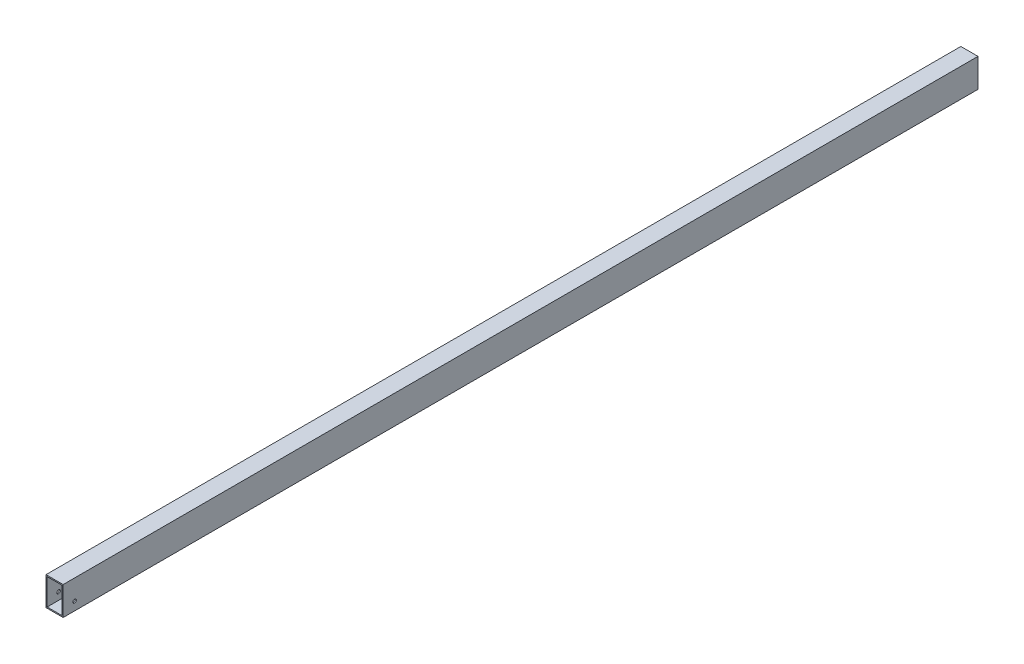
SolidWorks part; units mm, degrees
material "1060 合金"
ref_plane "前视基准面" through (0, 0, 0) normal (0, 0, 1) x (1, 0, 0)
ref_plane "上视基准面" through (0, 0, 0) normal (0, 1, 0) x (1, 0, 0)
ref_plane "右视基准面" through (0, 0, 0) normal (1, 0, 0) x (0, 0, -1)
other "Configuration Table"
sketch "草图1" plane through (0, 0, 0) normal (0, 0, 1) x (1, 0, 0)
  line L1 (0, 0) -> (15, 0)
  line L2 (0, 0) -> (0, -25)
  line L3 (0, -25) -> (15, -25)
  line L4 (15, 0) -> (15, -25)
  dimension "D1" = 25
  dimension "D2" = 15
extrude "拉伸-薄壁1" add sketch "草图1" along normal blind 800 thin thin type one direction reverse wall 1
sketch "草图2" plane through (0, -25, 0) normal (0, -1, 0) x (1, 0, 0)
  circle A1 centre (7.5, 825) radius 2.6
  circle A2 centre (7.5, 825) radius 2.6
  dimension "D1" = 0
extrude "切除-拉伸1" [suppressed] cut sketch "草图2" against normal up to next
sketch "草图3" plane through (0, 0, 0) normal (-1, 0, 0) x (0, 0, 1)
  line L0 (800, 0) -> (0, 0) construction
  line L1 (0, 0) -> (0, -25) construction
  circle A0 centre (215, -7.5) radius 1.7
  circle A1 centre (170, -7.5) radius 1.7
  dimension "D1" = 3.4
  dimension "D2" = 3.4
  dimension "D3" = 45
  dimension "D4" = 7.5
  dimension "D5" = 7.5
  dimension "D6" = 170
sketch "草图4" plane through (15, 0, 0) normal (1, 0, 0) x (0, 0, -1)
  line L0 (-800, -25) -> (0, -25) construction
  line L1 (-800, -25) -> (-800, 0) construction
  circle A0 centre (-790, -17.5) radius 1.5
  dimension "D1" = 3
  dimension "D2" = 7.5
  dimension "D3" = 10
extrude "切除-拉伸3" cut sketch "草图4" against normal through all
